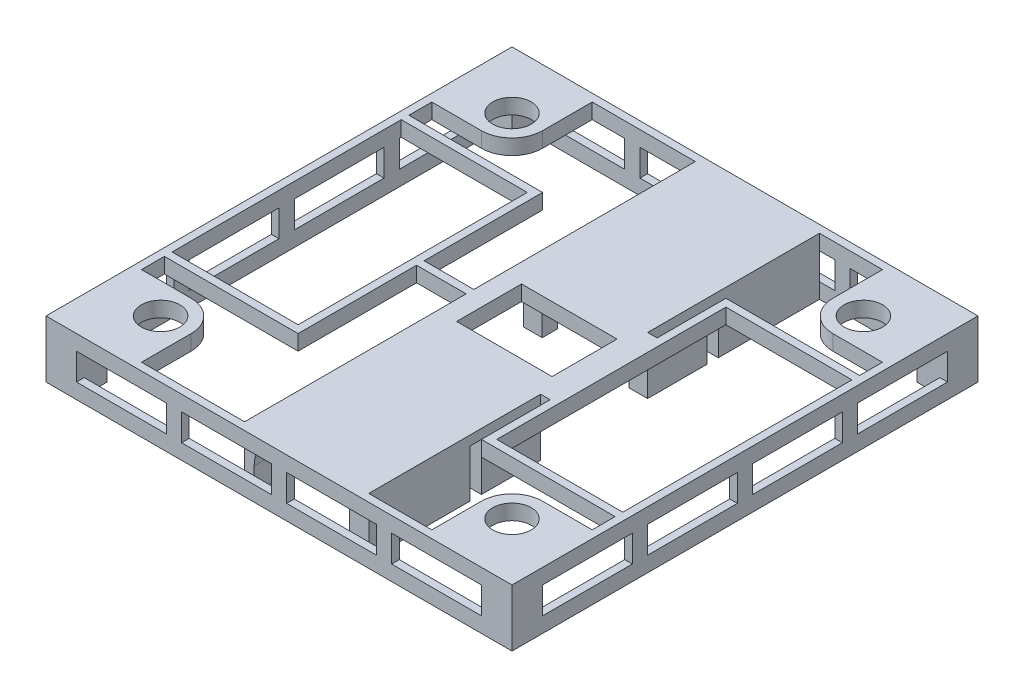
SolidWorks part; units mm, degrees
ref_plane "Front Plane" through (0, 0, 0) normal (0, 0, 1) x (1, 0, 0)
ref_plane "Top Plane" through (0, 0, 0) normal (0, 1, 0) x (1, 0, 0)
ref_plane "Right Plane" through (0, 0, 0) normal (1, 0, 0) x (0, 0, -1)
sketch "Sketch1" plane through (0, 0, 0) normal (0, 1, 0) x (1, 0, 0)
  line L0 (0, 0) -> (122, 0)
  line L1 (0, 0) -> (0, 122)
  line L2 (122, 0) -> (122, 122)
  line L3 (0, 122) -> (122, 122)
  line L4 (2, 2) -> (120, 2)
  line L5 (120, 2) -> (120, 120)
  line L6 (2, 120) -> (120, 120)
  line L7 (2, 2) -> (2, 120)
  dimension "D1" = 2
extrude "Boss-Extrude2" add sketch "Sketch1" along normal blind 15 contours L3 L1 L0 L2 L4 L7 L6 L5 region at (1.7253, 0, -61)
sketch "Sketch4" plane through (0, 0, 0) normal (0, 0, 1) x (1, 0, 0)
  line L0 (0, 15) -> (8, 15)
  line L1 (0, 15) -> (122, 15) construction
  line L2 (8, 15) -> (8, 0)
  line L3 (0, 0) -> (122, 0) construction
  line L4 (8, 15) -> (8, 11)
  line L5 (8, 11) -> (114, 11)
  line L6 (114, 11) -> (114, 4)
  line L7 (114, 4) -> (8, 4)
extrude "Cut-Extrude1" cut sketch "Sketch4" against normal through all both and the other way through all contours L7 L6 L5 L2 region at (61, 7.5, 0)
sketch "Sketch5" plane through (0, 0, 0) normal (-1, 0, 0) x (0, 0, 1)
  line L0 (-122, 15) -> (-114, 15)
  line L1 (0, 15) -> (-122, 15) construction
  line L2 (-114, 15) -> (-114, 0)
  line L3 (0, 0) -> (-122, 0) construction
  line L4 (-114, 0) -> (-8, 0)
  line L5 (-8, 0) -> (-8, 11)
  line L6 (-8, 11) -> (-114, 11)
  line L7 (-114, 11) -> (-114, 4)
  line L8 (-114, 4) -> (-8, 4)
extrude "Cut-Extrude2" cut sketch "Sketch5" against normal through all both and the other way through all contours L2 L8 L5 L6 region at (0, 7.5, -61)
sketch "Sketch6" plane through (0, 15, 0) normal (0, 1, 0) x (1, 0, 0)
  line L0 (0, 122) -> (8, 122)
  line L1 (0, 122) -> (0, 114)
  line L2 (8, 122) -> (8, 114)
  line L3 (0, 114) -> (8, 114)
  line L4 (0, 122) -> (122, 122) construction
  line L5 (61, 122) -> (61, 110.513)
  line L6 (122, 61) -> (106.27, 61)
  line L7 (122, 0) -> (122, 122) construction
  line L8 (122, 114) -> (114, 114)
  line L9 (114, 122) -> (114, 114)
  line L10 (122, 122) -> (122, 114)
  line L11 (122, 122) -> (114, 122)
  line L12 (122, 0) -> (114, 0)
  line L13 (122, 0) -> (122, 8)
  line L14 (114, 0) -> (114, 8)
  line L15 (122, 8) -> (114, 8)
  line L16 (61, 0) -> (61, 11.487)
  line L17 (0, 8) -> (8, 8)
  line L18 (8, 0) -> (8, 8)
  line L19 (0, 0) -> (0, 8)
  line L20 (0, 0) -> (8, 0)
  line M11 (120, 2) -> (2, 2)
  line M12 (2, 2) -> (2, 120)
  line M13 (2, 120) -> (120, 120)
  line M14 (120, 120) -> (120, 2)
extrude "Boss-Extrude3" add sketch "Sketch6" against normal blind 15 contours L3 L2 M12 M13 | L9 L8 M13 M14 | L15 L14 M14 M11 | L18 L17 M11 M12 region at (5, 15, -117) region at (5, 15, -5) region at (117, 15, -117) region at (117, 15, -5)
sketch "Sketch7" plane through (0, 15, 0) normal (0, 1, 0) x (1, 0, 0)
  line L3 (15, 99) -> (0, 99)
  line L5 (0, 0) -> (0, 122) construction
  line L6 (23, 107) -> (23, 122)
  line L7 (0, 122) -> (122, 122) construction
  line L8 (23, 122) -> (0, 122)
  line L9 (0, 122) -> (0, 99)
  line L10 (61, 122) -> (61, 61)
  line L11 (107, 99) -> (122, 99)
  line L12 (122, 99) -> (122, 122)
  line L13 (122, 122) -> (99, 122)
  line L14 (99, 107) -> (99, 122)
  line L15 (99, 15) -> (99, 0)
  line L16 (99, 0) -> (122, 0)
  line L17 (122, 0) -> (122, 23)
  line L18 (107, 23) -> (122, 23)
  line L19 (15, 23) -> (0, 23)
  line L20 (0, 23) -> (0, 0)
  line L21 (0, 0) -> (23, 0)
  line L22 (23, 15) -> (23, 0)
  circle A0 centre (15, 107) radius 1.5
  circle A1 centre (15, 107) radius 8
  circle A2 centre (107, 107) radius 8
  circle A3 centre (107, 107) radius 1.5
  circle A4 centre (107, 15) radius 8
  circle A5 centre (107, 15) radius 1.5
  circle A6 centre (15, 15) radius 8
  circle A7 centre (15, 15) radius 1.5
  point P43 (61, 61)
  line M6 (114, 2) -> (8, 2)
  line M7 (8, 2) -> (8, 8)
  line M8 (8, 8) -> (2, 8)
  line M9 (2, 8) -> (2, 114)
  line M10 (2, 114) -> (8, 114)
  line M11 (8, 114) -> (8, 120)
  line M12 (8, 120) -> (114, 120)
  line M13 (114, 120) -> (114, 114)
  line M14 (114, 114) -> (120, 114)
  line M15 (120, 114) -> (120, 8)
  line M16 (120, 8) -> (114, 8)
  line M17 (114, 8) -> (114, 2)
  dimension "D1" = 4
extrude "Boss-Extrude4" add sketch "Sketch7" against normal blind 4 contours A1 L6 L3 M12 M11 M10 M9 | A1 A0 | A2 L11 L14 M15 M14 M13 M12 | A2 A3 | A4 A5 | A4 L15 L18 M6 M17 M16 M15 | A6 L19 L22 M9 M8 M7 M6 | A6 A7 region at (8.5, 15, -99.297) region at (9.5031, 15, -112.4969) region at (8.5, 15, -22.703) region at (20.4969, 15, -20.4969) region at (106.5, 15, -119.703) region at (107, 15, -114.7737) region at (99.297, 15, -8.5) region at (101.5031, 15, -20.4969)
sketch "Sketch8" plane through (0, 15, 0) normal (0, 1, 0) x (1, 0, 0)
  circle A0 centre (15, 15) radius 5.05
  circle A1 centre (107, 15) radius 5.05
  circle A2 centre (107, 107) radius 5.05
  circle A3 centre (15, 107) radius 5.05
extrude "Cut-Extrude3" cut sketch "Sketch8" against normal blind 4
sketch "Sketch9" plane through (122, 0, 0) normal (1, 0, 0) x (0, 0, -1)
  line L1 (8, 11) -> (8, 4)
  line L2 (114, 11) -> (114, 4)
  line L3 (8, 4) -> (114, 4)
  line L4 (61, 11) -> (61, 4)
  line L5 (61, 11) -> (63, 11)
  line L6 (63, 11) -> (63, 4)
  line L7 (63, 4) -> (59, 4)
  line L8 (59, 4) -> (59, 11)
  line L9 (8, 11) -> (6, 11)
  line L10 (6, 11) -> (61, 11)
  line L11 (6, 11) -> (61, 11)
  line L12 (35.5, 11) -> (35.5, 4)
  line L13 (31.5, 4) -> (31.5, 11)
  line L14 (33.5, 11) -> (35.5, 11)
  line L15 (35.5, 4) -> (31.5, 4)
  line L16 (33.5, 11) -> (33.5, 4)
  line L17 (88.5, 11) -> (90.5, 11)
  line L18 (90.5, 4) -> (86.5, 4)
  line L19 (88.5, 11) -> (88.5, 4)
  line L20 (90.5, 11) -> (90.5, 4)
  line L21 (86.5, 4) -> (86.5, 11)
  line M6 (8, 11) -> (114, 11)
extrude "Boss-Extrude5" add sketch "Sketch9" against normal blind 122 contours L16 L11 L13 L15 | L16 L3 L12 M6 | L6 L4 L3 M6 | L8 L3 L4 M6 | L20 L19 L3 M6 | L21 L18 L19 M6 region at (122, 7.5, -32.5) region at (122, 7.5, -34.5) region at (122, 7.5, -60) region at (122, 7.5, -62) region at (122, 7.5, -87.5) region at (122, 7.5, -89.5)
sketch "Sketch10" plane through (0, 0, 0) normal (0, -1, 0) x (1, 0, 0)
  line L0 (2, -31.5) -> (120, -31.5)
  line L1 (2, -31.5) -> (2, -92.7196)
  line L2 (120, -31.5) -> (120, -92.7196)
  line L3 (2, -92.7196) -> (120, -92.7196)
extrude "Cut-Extrude4" cut sketch "Sketch10" against normal through all both and the other way through all
sketch "Sketch11" plane through (0, 0, -122) normal (0, 0, -1) x (-1, 0, 0)
  line L0 (-61, 11) -> (-116, 11)
  line L1 (-8, 11) -> (-114, 11) construction
  line L2 (-88.5, 11) -> (-88.5, 4)
  line L3 (-114, 4) -> (-8, 4) construction
  line L4 (-88.5, 4) -> (-86.5, 4)
  line L5 (-86.5, 4) -> (-86.5, 11)
  line L6 (-86.5, 11) -> (-90.5, 11)
  line L7 (-90.5, 11) -> (-90.5, 4)
  line L8 (-90.5, 4) -> (-88.5, 4)
  line L9 (-59, 11) -> (-63, 11)
  line L10 (-61, 4) -> (-59, 4)
  line L11 (-59, 4) -> (-59, 11)
  line L12 (-63, 11) -> (-63, 4)
  line L13 (-61, 11) -> (-61, 4)
  line L14 (-63, 4) -> (-61, 4)
  line L15 (-31.5, 11) -> (-35.5, 11)
  line L16 (-33.5, 4) -> (-31.5, 4)
  line L17 (-31.5, 4) -> (-31.5, 11)
  line L18 (-35.5, 11) -> (-35.5, 4)
  line L19 (-33.5, 11) -> (-33.5, 4)
  line L20 (-35.5, 4) -> (-33.5, 4)
  line M6 (-8, 4) -> (-114, 4)
  line M8 (-114, 11) -> (-8, 11)
extrude "Boss-Extrude6" add sketch "Sketch11" against normal blind 122 contours L0 L7 L2 M6 | L5 L0 L2 M6 | L13 L11 M8 M6 | L13 L0 L12 M6 | L15 L19 L17 M6 | L19 L18 M8 M6 region at (62, 7.5, -122) region at (60, 7.5, -122) region at (87.5, 7.5, -122) region at (34.5, 7.5, -122) region at (89.5, 7.5, -122) region at (32.5, 7.5, -122)
sketch "Sketch12" plane through (0, 15, 0) normal (0, 1, 0) x (1, 0, 0)
  line L0 (99, 2) -> (23, 2)
  line L1 (99, 2) -> (99, 120)
  line L2 (23, 2) -> (23, 120)
  line L3 (99, 120) -> (23, 120)
extrude "Cut-Extrude5" cut sketch "Sketch12" against normal blind 122
sketch "Sketch13" plane through (0, 15, 0) normal (0, 1, 0) x (1, 0, 0)
  line L0 (61, 0) -> (61, 122)
  line L1 (0, 0) -> (122, 0) construction
  line L2 (0, 122) -> (122, 122) construction
  line L3 (15, 15) -> (107, 15)
  line L4 (61, 15) -> (61, 20)
  line L10 (61, 20) -> (56, 20)
  line L11 (56, 20) -> (56, 10)
  line L12 (56, 10) -> (66, 10)
  line L13 (66, 10) -> (66, 20)
  line L14 (66, 20) -> (61, 20)
  line L15 (61, 20) -> (61, 24.5)
  line L16 (61, 24.5) -> (55, 24.5)
  line L17 (61, 24.5) -> (69.5, 24.5)
  line L18 (69.5, 24.5) -> (69.5, 20)
  line L19 (69.5, 20) -> (66, 20)
  line L20 (56, 20) -> (55, 20)
  line L21 (55, 20) -> (55, 24.5)
  line L22 (55, 24.5) -> (55, 28.5)
  line L23 (55, 28.5) -> (50, 28.5)
  line L24 (50, 28.5) -> (50, 31)
  line L25 (50, 31) -> (55, 31)
  line L26 (55, 31) -> (55, 47)
  line L27 (55, 47) -> (77.5, 47)
  line L28 (77.5, 47) -> (77.5, 31)
  line L29 (77.5, 31) -> (82.5, 31)
  line L30 (82.5, 31) -> (82.5, 28.5)
  line L31 (82.5, 28.5) -> (77.5, 28.5)
  line L32 (77.5, 28.5) -> (77.5, 24.5)
  line L33 (77.5, 24.5) -> (69.5, 24.5)
  line L34 (61, 61) -> (120, 61)
  line L35 (120, 23) -> (120, 99) construction
  line L36 (61, 61) -> (2, 61)
  line L37 (2, 23) -> (2, 99) construction
  line L38 (62, 0) -> (62, 122)
  line L39 (61, 60) -> (2, 60)
  line L40 (61, 60) -> (120, 60)
  line L41 (60, 0) -> (60, 122)
  line L42 (61, 62) -> (2, 62)
  line L43 (61, 62) -> (120, 62)
  line L44 (77.5, 61) -> (77.5, 47)
  line L45 (82.5, 31) -> (82.5, 61)
  line L46 (82.5, 61) -> (82.5, 2)
  line L47 (23, 2) -> (99, 2) construction
  line L48 (82.5, 2) -> (77.5, 2)
  line L49 (77.5, 2) -> (77.5, 24.5)
  line L50 (55, 31) -> (55, 61)
  line L51 (55, 20) -> (55, 2)
  line L52 (55, 2) -> (50, 2)
  line L53 (50, 2) -> (50, 60)
  line M17 (99, 2) -> (23, 2)
  line M21 (2, 23) -> (2, 99)
  line M25 (23, 120) -> (99, 120)
  line M29 (120, 99) -> (120, 23)
  dimension "D1" = 1
  dimension "D2" = 1
extrude "Boss-Extrude7" add sketch "Sketch13" against normal blind 4 contours L41 L42 L36 M21 | L39 L50 L36 M21 | L50 L39 L41 L36 | L53 L25 L26 L50 L39 | L0 L42 L41 L36 | L41 L39 L0 L36 | L43 L0 L34 L38 | L0 L40 L38 L34 | L42 L0 L41 M25 | L0 L43 L38 M25 | L43 L38 L34 M29 | L44 L34 L38 L40 | L40 L0 L27 L38 | L41 L27 L0 L39 | L40 L45 L34 L44 | L45 L40 L34 M29 | L29 L45 L40 L44 L28 | L41 L16 L0 L27 | L17 L38 L27 L0 | L41 L10 L0 L16 | L14 L38 L17 L0 | L53 L3 L51 L21 L22 L23 | L41 L3 L0 L10 | L3 L38 L14 L0 | L41 L12 L0 L3 | L12 L38 L3 L0 | L38 L12 L0 M17 | L41 L0 L12 M17 | L49 L3 L46 L31 L32 | L49 L46 L3 M17 | L53 L51 L3 M17 region at (60.5, 15, -17.5) region at (61.5, 15, -12.5) region at (60.5, 15, -12.5) region at (61.5, 15, -17.5) region at (60.5, 15, -22.25) region at (61.5, 15, -22.25) region at (61.5, 15, -6) region at (60.5, 15, -6) region at (60.5, 15, -35.75) region at (61.5, 15, -35.75) region at (60.5, 15, -53.5) region at (61.5, 15, -53.5) region at (52.5, 15, -8.5) region at (52.5, 15, -21.75) region at (80, 15, -21.75) region at (80, 15, -8.5) region at (60.5, 15, -60.5) region at (61.5, 15, -60.5) region at (60.5, 15, -61.5) region at (61.5, 15, -61.5) region at (57.5, 15, -60.5) region at (69.75, 15, -60.5) region at (52.5, 15, -45.5) region at (80, 15, -45.5) region at (60.5, 15, -91) region at (61.5, 15, -91) region at (91, 15, -61.5) region at (31, 15, -61.5) region at (28.5, 15, -60.5) region at (80, 15, -60.5) region at (101.25, 15, -60.5)
sketch "Sketch14" plane through (0, 15, 0) normal (0, 1, 0) x (1, 0, 0)
  line L0 (77.5, 47) -> (55, 47)
  line L1 (55, 47) -> (55, 49)
  line L2 (55, 49) -> (77.5, 49)
  line L3 (77.5, 49) -> (82.5, 49)
  line L4 (82.5, 49) -> (82.5, 2)
  line L5 (82.5, 2) -> (77.5, 2)
  line L6 (77.5, 2) -> (77.5, 47)
  line L7 (55, 49) -> (50, 49)
  line L8 (50, 49) -> (50, 2)
  line L9 (50, 2) -> (55, 2)
  line L10 (55, 2) -> (55, 47)
  line L11 (69.5, 20) -> (69.5, 24.5)
  line L12 (69.5, 24.5) -> (77.5, 24.5)
  line L13 (69.5, 20) -> (77.5, 20)
extrude "Boss-Extrude8" add sketch "Sketch14" against normal blind 15 contours L9 L10 L1 L7 L8 | L6 L5 L4 L3 L2 L1 L0 | L11 L13 L6 L12 region at (77.7902, 15, -29.1161) region at (52.5, 15, -25.5) region at (73.5, 15, -22.25)
sketch "Sketch16" plane through (0, 0, -24.5) normal (0, 0, -1) x (-1, 0, 0)
  line L0 (-69.5, 0) -> (-55, 0)
  line L1 (-55, 0) -> (-55, 12.5)
  line L2 (-55, 12.5) -> (-69.5, 12.5)
  line L3 (-69.5, 0) -> (-69.5, 15) construction
  line L4 (-69.5, 12.5) -> (-69.5, 0)
  line L5 (-55, 12.5) -> (-61, 12.5)
  line L6 (-61, 12.5) -> (-61, 6.25)
  line L7 (-61, 6.25) -> (-66.5, 6.25)
  line L8 (-66.5, 9.25) -> (-66.5, 3.25)
  line L9 (-66.5, 9.25) -> (-61, 9.25)
  line L10 (-66.5, 3.25) -> (-61, 3.25)
  line L11 (-61, 9.25) -> (-61, 3.25)
  circle A0 centre (-66.5, 6.25) radius 3
  circle A1 centre (-61, 6.25) radius 6
  line M16 (-69.5, 0) -> (-69.5, 15)
extrude "Boss-Extrude11" add sketch "Sketch16" against normal blind 4.5 contours A1 L6 L2 L4 A0 L9 | A1 L1 L2 L6 | A1 L10 A0 L0 L1 M16 region at (69.3421, 3.125, -24.5) region at (66.9472, 10.8714, -24.5) region at (56.6101, 11.148, -24.5)
sketch "Sketch17" plane through (0, 12.5, 0) normal (0, 1, 0) x (1, 0, 0)
  line L0 (55, 20) -> (55, 24.5)
  line L1 (55, 20) -> (69.5, 20)
  line L2 (55, 24.5) -> (69.5, 24.5)
  line L3 (69.5, 20) -> (69.5, 24.5)
  line L4 (55, 24.5) -> (60, 24.5) construction
  line L5 (55, 20) -> (55, 24.5) construction
extrude "Boss-Extrude12" add sketch "Sketch17" along normal blind 2.5
sketch "Sketch18" plane through (0, 11, 0) normal (0, -1, 0) x (1, 0, 0)
  line L0 (62, -2) -> (62, -47)
  line L1 (62, -2) -> (60, -2)
  line L2 (62, -47) -> (60, -47)
  line L3 (60, -2) -> (60, -47)
  line L4 (62, -2) -> (62, -47) construction
extrude "Cut-Extrude6" cut sketch "Sketch18" against normal blind 2
sketch "Sketch19" plane through (55, 0, 0) normal (1, 0, 0) x (0, 0, -1)
  line L0 (47, 0) -> (47, 12.5)
  line L1 (47, 12.5) -> (2, 12.5)
  line L2 (2, 11) -> (2, 15) construction
  line L3 (2, 12.5) -> (2, 15)
  line L4 (2, 15) -> (47, 15)
  line L5 (47, 15) -> (47, 12.5)
  line M1 (47, 15) -> (24.5, 15)
  line M2 (24.5, 15) -> (24.5, 6.25)
  line M5 (47, 0) -> (47, 15)
extrude "Boss-Extrude13" add sketch "Sketch19" along normal blind 25 contours L4 L3 L1 M2 | L1 M5 M1 M2 region at (55, 13.75, -35.75) region at (55, 13.75, -13.25)
sketch "Sketch21" plane through (0, 0, 0) normal (0, -1, 0) x (1, 0, 0)
  line L0 (77.5, -24.5) -> (77.5, -28.5)
  line L1 (77.5, -24.5) -> (77.5, -47) construction
  line L2 (77.5, -28.5) -> (82.5, -28.5)
  line L3 (82.5, -49) -> (82.5, -2) construction
  line L4 (82.5, -28.5) -> (82.5, -31)
  line L5 (82.5, -31) -> (50, -31)
  line L6 (50, -49) -> (50, -2) construction
  line L7 (50, -31) -> (50, -28.5)
  line L8 (50, -28.5) -> (77.5, -28.5)
  line M1 (55, -47) -> (55, -24.5)
  line M3 (77.5, -24.5) -> (77.5, -47)
  line M11 (50, -2) -> (50, -49)
  line M13 (82.5, -49) -> (82.5, -2)
extrude "Cut-Extrude7" cut sketch "Sketch21" against normal blind 12.5 contours L5 L2 M13 M3 | L8 L5 M11 M1 region at (80, 0, -29.75) region at (52.5, 0, -29.75)
sketch "Sketch26" plane through (0, 12.5, 0) normal (0, -1, 0) x (1, 0, 0)
  line L0 (55, -20) -> (47.6546, -20)
  line L1 (55, -20) -> (55, -2)
  line L2 (47.6546, -20) -> (47.6546, -2)
  line L3 (55, -2) -> (47.6546, -2)
extrude "Cut-Extrude8" cut sketch "Sketch26" along normal blind 25
sketch "Sketch27" plane through (0, 0, -20) normal (0, 0, 1) x (1, 0, 0)
  line L0 (50, 0) -> (50, 12.5)
  line L1 (50, 0) -> (55.7303, 0)
  line L2 (50, 12.5) -> (55.7303, 12.5)
  line L3 (55.7303, 0) -> (55.7303, 12.5)
  circle A0 centre (61, 6.25) radius 8.5
  line M10 (50, 12.5) -> (50, 0)
  line M11 (50, 0) -> (77.5, 0)
extrude "Boss-Extrude14" add sketch "Sketch27" along normal blind 18 contours A0 L2 M10 M11 region at (51.7659, 6.25, -20)
sketch "Sketch29" plane through (0, 0, -20) normal (0, 0, 1) x (1, 0, 0)
  circle A0 centre (61, 6.25) radius 8.5
extrude "Cut-Extrude9" cut sketch "Sketch29" along normal blind 18
sketch "Sketch30" plane through (0, 0, 0) normal (0, -1, 0) x (1, 0, 0)
  line L0 (55, -24.5) -> (77.5, -24.5)
  line L1 (55, -24.5) -> (55, -20)
  line L2 (77.5, -24.5) -> (77.5, -20)
  line L3 (55, -20) -> (77.5, -20)
extrude "Cut-Extrude10" cut sketch "Sketch30" against normal blind 6.35
sketch "Sketch31" plane through (0, 0, -20) normal (0, 0, -1) x (-1, 0, 0)
  line L0 (-55, 0) -> (-55.2391, 0)
  line L1 (-55, 0) -> (-55, 0.3342)
  line L2 (-55.2391, 0) -> (-55.2391, 0.3342)
  line L3 (-55, 0.3342) -> (-55.2391, 0.3342)
extrude "Cut-Extrude11" cut sketch "Sketch31" against normal up to surface (18 mm away) up to face at (65.1774, 7.3143, -2)
sketch "Sketch32" plane through (0, 0, -2) normal (0, 0, 1) x (1, 0, 0)
  line L0 (52.5, 6.25) -> (61, 6.25)
  line L1 (52.5, 6.25) -> (52.5, -7.1759)
  line L2 (61, 6.25) -> (61, -7.1759)
  line L3 (52.5, -7.1759) -> (61, -7.1759)
  arc A0 (53.9511, 11) -> (52.8032, 4) centre (61, 6.25) ccw construction
extrude "Cut-Extrude12" cut sketch "Sketch32" against normal up to surface (18 mm away) up to face at (63.6001, 9.7082, -20)
sketch "Sketch34" plane through (0, 0, 0) normal (0, -1, 0) x (1, 0, 0)
  line L0 (55, -47) -> (55, -43)
  line L1 (55, -31) -> (55, -47) construction
  line L2 (55, -43) -> (50, -43)
  line L3 (50, -49) -> (50, -31) construction
  line L4 (50, -43) -> (50, -41)
  line L5 (50, -41) -> (55, -41)
  line L6 (55, -41) -> (55, -43)
  line M4 (55, -47) -> (55, -31)
  line M6 (50, -31) -> (50, -49)
extrude "Cut-Extrude13" cut sketch "Sketch34" against normal up to surface (12.5 mm away) contours L5 L2 M6 M4 region at (52.5, 0, -42) up to face at (64.9375, 12.5, -29.375)
sketch "Sketch36" plane through (0, 15, 0) normal (0, 1, 0) x (1, 0, 0)
  line L0 (2, 60) -> (2, 62)
  line L1 (2, 62) -> (2, 61)
  line L2 (2, 61) -> (2, 31)
  line L3 (2, 31) -> (35, 31)
  line L4 (35, 31) -> (35, 91)
  line L5 (35, 91) -> (2, 91)
  line L6 (2, 62) -> (2, 99) construction
  line L7 (2, 91) -> (2, 62)
  line M15 (2, 60) -> (50, 60)
  line M29 (60, 62) -> (2, 62)
extrude "Cut-Extrude14" cut sketch "Sketch36" against normal blind 6.35 contours L4 L0 M15 M29 region at (18.5, 15, -61)
sketch "Sketch37" plane through (0, 15, 0) normal (0, 1, 0) x (1, 0, 0)
  line L0 (35, 62) -> (35, 91)
  line L1 (35, 91) -> (2, 91)
  line L2 (2, 23) -> (2, 99) construction
  line L3 (2, 91) -> (2, 93)
  line L4 (2, 93) -> (37, 93)
  line L5 (37, 93) -> (37, 29)
  line L6 (37, 29) -> (2, 29)
  line L7 (2, 29) -> (2, 31)
  line L8 (2, 31) -> (35, 31)
  line L9 (35, 31) -> (35, 62)
  line L10 (2, 93) -> (2, 29)
  line M31 (2, 23) -> (2, 99)
  line M37 (60, 62) -> (35, 62)
  line M38 (35, 62) -> (35, 60)
  line M39 (35, 60) -> (50, 60)
extrude "Boss-Extrude15" add sketch "Sketch37" against normal blind 4 contours L5 L4 L1 L0 M31 M37 | L5 M37 M38 M39 | L9 L8 L6 L5 M31 M39 region at (36, 15, -61) region at (35.4675, 15, -76.5) region at (36, 15, -59.5325)
sketch "Sketch38" plane through (0, 15, 0) normal (0, 1, 0) x (1, 0, 0)
  line L0 (120, 60) -> (87, 60)
  line L1 (82.5, 60) -> (120, 60) construction
  line L2 (87, 60) -> (87, 31)
  line L3 (87, 31) -> (120, 31)
  line L4 (120, 23) -> (120, 60) construction
  line L5 (120, 31) -> (120, 29)
  line L6 (120, 29) -> (85, 29)
  line L7 (85, 29) -> (85, 93)
  line L8 (85, 93) -> (120, 93)
  line L9 (120, 62) -> (120, 99) construction
  line L10 (120, 93) -> (120, 91)
  line L11 (120, 91) -> (87, 91)
  line L12 (87, 91) -> (87, 60)
  line L13 (120, 93) -> (120, 91)
  line L14 (120, 31) -> (120, 29)
extrude "Boss-Extrude16" add sketch "Sketch38" against normal blind 4 contours L12 L11 L10 L8 L7 L6 L5 L3 L2 region at (86.2705, 15, -45.5)
sketch "Sketch39" plane through (0, 15, 0) normal (0, 1, 0) x (1, 0, 0)
  line L0 (87, 62) -> (87, 60)
  line L1 (87, 62) -> (120, 62)
  line L2 (87, 60) -> (120, 60)
  line L3 (120, 62) -> (120, 60)
extrude "Cut-Extrude15" cut sketch "Sketch39" against normal blind 4
sketch "Sketch41" plane through (0, 11, 0) normal (0, -1, 0) x (-1, 0, 0)
  line L0 (-82.5, 60) -> (-82.5, 49)
  line L1 (-82.5, 49) -> (-82.5, 62)
  line L2 (-62, 62) -> (-85, 62) construction
  line L3 (-82.5, 62) -> (-82.5, 73)
  line L4 (-82.5, 73) -> (-50, 73)
  line L5 (-50, 73) -> (-50, 79)
  line L6 (-50, 79) -> (-55, 79)
  line L7 (-55, 79) -> (-55, 75)
  line L8 (-55, 75) -> (-77.5, 75)
  line L9 (-77.5, 75) -> (-77.5, 91)
  line L10 (-77.5, 91) -> (-82.5, 91)
  line L11 (-82.5, 91) -> (-82.5, 73)
  line L12 (-82.5, 91) -> (-82.5, 93.5)
  line L13 (-82.5, 93.5) -> (-77.5, 93.5)
  line L14 (-77.5, 93.5) -> (-77.5, 120)
  line L15 (-8, 120) -> (-114, 120) construction
  line L16 (-77.5, 120) -> (-82.5, 120)
  line L17 (-82.5, 120) -> (-82.5, 93.5)
  line L18 (-55, 79) -> (-55, 81)
  line L19 (-55, 81) -> (-50, 81)
  line L20 (-50, 81) -> (-50, 91)
  line L21 (-50, 91) -> (-55, 91)
  line L22 (-55, 91) -> (-55, 81)
  line L23 (-55, 91) -> (-55, 93.5)
  line L24 (-55, 93.5) -> (-50, 93.5)
  line L25 (-50, 93.5) -> (-50, 120)
  line L26 (-50, 120) -> (-55, 120)
  line L27 (-55, 120) -> (-55, 93.5)
  line L28 (-55, 93.5) -> (-55, 102)
extrude "Boss-Extrude17" add sketch "Sketch41" along normal blind 11 and the other way blind 4 contours L10 L11 L4 L5 L6 L7 L8 L9 | L16 L17 L13 L14 | L21 L22 L19 L20 | L26 L27 L24 L25 region at (82.1285, 11, -82) region at (80, 11, -106.75) region at (52.5, 11, -106.75) region at (52.5, 11, -86)
sketch "Sketch42" plane through (0, 15, 0) normal (0, 1, 0) x (1, 0, 0)
  line L0 (50, 73) -> (50, 120)
  line L1 (50, 73) -> (82.5, 73)
  line L2 (50, 120) -> (82.5, 120)
  line L3 (82.5, 73) -> (82.5, 120)
  line L4 (82.5, 73) -> (82.5, 62)
  line L5 (62, 62) -> (85, 62) construction
  line L6 (82.5, 62) -> (77.5, 62)
  line L7 (77.5, 62) -> (77.5, 73)
  line L8 (77.5, 73) -> (82.5, 73)
  line L9 (50, 73) -> (50, 62)
  line L10 (60, 62) -> (37, 62) construction
  line L11 (50, 62) -> (55, 62)
  line L12 (55, 62) -> (55, 73)
extrude "Boss-Extrude18" add sketch "Sketch42" against normal blind 2.5 contours L1 L3 L2 L0 | L7 L6 L4 L1 | L11 L12 L1 L9 region at (66.25, 15, -96.5) region at (52.5, 15, -67.5) region at (80, 15, -67.5)
sketch "Sketch46" plane through (0, 12.5, 0) normal (0, -1, 0) x (1, 0, 0)
  line L0 (82.5, -62) -> (77.5, -62)
  line L1 (82.5, -62) -> (82.5, -73)
  line L2 (77.5, -62) -> (77.5, -73)
  line L3 (82.5, -73) -> (77.5, -73)
  line L4 (82.5, -62) -> (77.5, -62) construction
  line L5 (55, -73) -> (50, -73)
  line L6 (55, -73) -> (55, -62)
  line L7 (50, -73) -> (50, -62)
  line L8 (55, -62) -> (50, -62)
extrude "Boss-Extrude19" add sketch "Sketch46" along normal blind 1.5
sketch "Sketch47" plane through (0, 11, 0) normal (0, -1, 0) x (1, 0, 0)
  line L0 (62, -75) -> (60, -75)
  line L1 (62, -75) -> (62, -120)
  line L2 (60, -75) -> (60, -120)
  line L3 (62, -120) -> (60, -120)
extrude "Cut-Extrude16" cut sketch "Sketch47" against normal blind 1.5
sketch "Sketch50" plane through (0, 12.5, 0) normal (0, -1, 0) x (1, 0, 0)
  line L0 (77.5, -75) -> (77.5, -97.6)
  line L1 (77.5, -93.5) -> (77.5, -120) construction
  line L2 (77.5, -97.6) -> (55, -97.6)
  line L3 (55, -120) -> (55, -93.5) construction
  line L4 (55, -97.6) -> (55, -102.6)
  line L5 (55, -102.6) -> (77.5, -102.6)
  line L6 (77.5, -102.6) -> (77.5, -97.6)
  line M5 (55, -93.5) -> (55, -120)
  line M7 (77.5, -120) -> (77.5, -93.5)
extrude "Boss-Extrude21" add sketch "Sketch50" along normal blind 6.15 contours L5 L2 M5 M7 region at (66.25, 12.5, -100.1)
sketch "Sketch53" plane through (0, 0, -97.6) normal (0, 0, 1) x (1, 0, 0)
  line L0 (55, 12.5) -> (55, 0)
  line L1 (55, 0) -> (67, 0)
  line L2 (67, 0) -> (67, 12.5)
  line L3 (77.5, 12.5) -> (55, 12.5) construction
  line L4 (67, 12.5) -> (55, 12.5)
  line L5 (61, 0) -> (61, 6.25)
  line L6 (61, 6.25) -> (66.5, 6.25)
  line L7 (66.5, 3.25) -> (61, 3.25)
  line L8 (66.5, 9.25) -> (63.3151, 9.25)
  circle A0 centre (61, 6.25) radius 6.0008
  circle A1 centre (66.5, 6.25) radius 3
  line M9 (55, 6.35) -> (77.5, 6.35)
extrude "Cut-Extrude17" cut sketch "Sketch53" against normal blind 6.15 contours A1 A0 L2 M9 | A1 L6 L5 L7 A0 | A1 L0 A0 L5 L6 M9 | A1 A0 M9 | A1 L2 M9 | L2 A1 A0 M9 | L2 A1 A0 | A0 A1 L2 | A1 A0 L7 | A1 L8 A0 | L5 A0 L7 | A1 region at (58.4764, 3.7789, -97.6) region at (60.321, 9.0571, -97.6) region at (66.2759, 9.2456, -97.6) region at (65.3618, 5.0861, -97.6) region at (68.0379, 7.519, -97.6) region at (66.7619, 8.5047, -97.6) region at (63.0356, 2.0195, -97.6) region at (62.6426, 4.5803, -97.6) region at (68.0561, 5.0898, -97.6) region at (66.2759, 3.2544, -97.6) region at (66.7619, 3.9953, -97.6)
sketch "Sketch54" plane through (0, 0, -102.6) normal (0, 0, -1) x (-1, 0, 0)
  circle A0 centre (-61, 6.25) radius 8.5
extrude "Cut-Extrude18" cut sketch "Sketch54" along normal up to surface (17.4 mm away) up to face at (33, 7.5, -120)
sketch "Sketch57" plane through (0, 0, 0) normal (0, -1, 0) x (1, 0, 0)
  line L0 (82.5, -2) -> (82.5, -49)
  line L1 (82.5, -49) -> (82.5, -73)
  line L2 (82.5, -73) -> (82.5, -120)
  line L3 (82.5, -73) -> (82.5, -75)
  line L4 (82.5, -75) -> (50, -75)
  line L5 (50, -73) -> (50, -79) construction
  line L6 (50, -75) -> (50, -47)
  line L7 (50, -49) -> (50, -43) construction
  line L8 (50, -47) -> (82.5, -47)
  line M2 (50, -43) -> (50, -49)
  line M3 (50, -49) -> (82.5, -49)
  line M4 (82.5, -49) -> (82.5, -31)
  line M7 (77.5, -47) -> (55, -47)
extrude "Cut-Extrude20" cut sketch "Sketch57" against normal up to surface (12.5 mm away) contours L8 M2 M3 M4 M7 | L6 L4 L2 L1 M3 region at (66.25, 0, -48) region at (66.25, 0, -62) up to face at (62.8125, 12.5, -87.7)
sketch "Sketch58" plane through (0, 12.5, 0) normal (0, -1, 0) x (1, 0, 0)
  line L0 (77.5, -49) -> (77.5, -73)
  line L1 (77.5, -49) -> (55, -49)
  line L2 (77.5, -73) -> (55, -73)
  line L3 (55, -49) -> (55, -73)
extrude "Cut-Extrude21" cut sketch "Sketch58" against normal through all both and the other way through all
sketch "Sketch62" plane through (0, 12.5, 0) normal (0, -1, 0) x (1, 0, 0)
  line L0 (82.5, -47) -> (82.5, -75)
  line L1 (82.5, -47) -> (50, -47)
  line L2 (82.5, -75) -> (50, -75)
  line L3 (50, -47) -> (50, -75)
  line L4 (77.5, -49) -> (77.5, -73)
  line L5 (77.5, -49) -> (55, -49)
  line L6 (77.5, -73) -> (55, -73)
  line L7 (55, -49) -> (55, -73)
extrude "Boss-Extrude22" add sketch "Sketch62" along normal blind 1.5
sketch "Sketch63" plane through (0, 11, 0) normal (0, -1, 0) x (-1, 0, 0)
  line L0 (-82.5, 47) -> (-85, 47)
  line L1 (-85, 29) -> (-85, 60) construction
  line L2 (-85, 47) -> (-82.5, 75)
  line L3 (-82.5, 75) -> (-85, 75)
  line L4 (-85, 62) -> (-85, 93) construction
  line L5 (-85, 75) -> (-85, 47)
  line L6 (-55, 49) -> (-80, 49)
  line L7 (-80, 49) -> (-80, 73)
  line L8 (-80, 73) -> (-77.5, 73)
  line L9 (-77.5, 73) -> (-77.5, 49)
  line L10 (-82.5, 47) -> (-82.5, 75)
extrude "Boss-Extrude23" add sketch "Sketch63" against normal blind 4 contours L0 L10 L2 | L3 L5 L2 region at (83.3333, 11, -56.3333) region at (84.1667, 11, -65.6667)
sketch "Sketch64" plane through (0, 11, 0) normal (0, -1, 0) x (1, 0, 0)
  line L0 (55, -61) -> (80, -61)
  line L1 (55, -49) -> (55, -73) construction
  line L2 (80, -61) -> (80, -52.5)
  line L3 (80, -52.5) -> (55, -52.5)
  line L4 (55, -52.5) -> (55, -61)
  line L5 (55, -61) -> (55, -69.5)
  line L6 (55, -69.5) -> (80, -69.5)
  line L7 (80, -69.5) -> (80, -61)
extrude "Cut-Extrude22" cut sketch "Sketch64" against normal blind 4 contours L3 L4 L0 L2 | L6 L7 L0 L5 region at (67.5, 11, -56.75) region at (67.5, 11, -65.25)
sketch "Sketch65" plane through (0, 11, 0) normal (0, -1, 0) x (-1, 0, 0)
  line L0 (-77.5, 52.5) -> (-55, 52.5)
  line L1 (-55, 49) -> (-55, 73) construction
  line L2 (-55, 52.5) -> (-55, 49)
  line L3 (-55, 49) -> (-77.5, 49)
  line L4 (-77.5, 49) -> (-77.5, 52.5)
  line L5 (-80, 61) -> (-73.3948, 61)
  line L6 (-80, 69.5) -> (-80, 52.5) construction
  line L7 (-77.5, 73) -> (-77.5, 69.5)
  line L8 (-55, 73) -> (-77.5, 73)
  line L9 (-55, 69.5) -> (-55, 73)
  line L10 (-77.5, 69.5) -> (-55, 69.5)
extrude "Boss-Extrude24" add sketch "Sketch65" against normal blind 4 contours L4 L3 L2 L0 | L7 L10 L9 L8 region at (66.25, 11, -50.75) region at (66.25, 11, -71.25)
sketch "Sketch67" plane through (0, 0, -102.6) normal (0, 0, -1) x (-1, 0, 0)
  line L4 (-52.5, 6.25) -> (-52.5, -3.5632)
  line L5 (-52.5, -3.5632) -> (-56.7117, -1.0889)
  circle A1 centre (-61, 6.25) radius 8.5
  arc M13 (-55, 0.2292) -> (-55, 12.2708) centre (-61, 6.25) ccw
extrude "Cut-Extrude23" cut sketch "Sketch67" along normal up to surface (17.4 mm away) contours A1 L5 L4 M13 region at (53.7639, -0.2943, -102.6) up to face at (33, 7.5, -120)
sketch "Sketch68" plane through (0, 0, 0) normal (0, -1, 0) x (1, 0, 0)
  line L0 (82.5, -31) -> (77.5, -31)
  line L1 (82.5, -31) -> (82.5, -31.5)
  line L2 (77.5, -31) -> (77.5, -31.5)
  line L3 (82.5, -31.5) -> (77.5, -31.5)
  line L4 (55, -31) -> (50, -31)
  line L5 (50, -31) -> (50, -31.5)
  line L6 (50, -41) -> (50, -31) construction
  line L7 (50, -31.5) -> (55, -31.5)
  line L8 (55, -31) -> (55, -41) construction
  line L9 (55, -31.5) -> (55, -31)
  line L10 (77.5, -31) -> (77.5, -91)
  line L11 (77.5, -75) -> (77.5, -91) construction
  line L12 (77.5, -91) -> (77.5, -61)
  line L13 (77.5, -61) -> (71.7624, -61)
  line L14 (55, -90.5) -> (55, -91)
  line L15 (50, -90.5) -> (55, -90.5)
  line L16 (50, -91) -> (50, -90.5)
  line L17 (55, -91) -> (50, -91)
  line L18 (82.5, -90.5) -> (77.5, -90.5)
  line L19 (77.5, -91) -> (77.5, -90.5)
  line L20 (82.5, -91) -> (82.5, -90.5)
  line L21 (82.5, -91) -> (77.5, -91)
  line M4 (82.5, -47) -> (82.5, -31)
  line M5 (82.5, -31) -> (77.5, -31)
  line M6 (77.5, -31) -> (77.5, -47)
extrude "Cut-Extrude24" cut sketch "Sketch68" against normal up to surface (12.5 mm away) contours L3 M4 M5 M6 | L7 L9 L4 L5 | L17 L14 L15 L16 | L21 L20 L18 L12 region at (80, 0, -31.25) region at (80, 0, -90.75) region at (52.5, 0, -31.25) region at (52.5, 0, -90.75) up to face at (62.8125, 12.5, -87.7)
sketch "Sketch69" plane through (0, 0, 0) normal (0, -1, 0) x (-1, 0, 0)
  line L0 (-77.5, 31.5) -> (-77.6, 31.5)
  line L1 (-77.5, 31.5) -> (-82.5, 31.5) construction
  line L2 (-77.6, 31.5) -> (-77.6, 47)
  line L3 (-77.5, 47) -> (-82.5, 47) construction
  line L4 (-77.6, 47) -> (-77.5, 47)
  line L5 (-77.5, 47) -> (-77.5, 31.5)
  line L6 (-55, 31.5) -> (-54.9, 31.5)
  line L7 (-50, 31.5) -> (-55, 31.5) construction
  line L8 (-54.9, 31.5) -> (-54.9, 47)
  line L9 (-50, 47) -> (-55, 47) construction
  line L10 (-54.9, 47) -> (-55, 47)
  line L11 (-55, 47) -> (-55, 31.5)
  line L12 (-80, 61) -> (-77.55, 61)
  line L13 (-80, 69.5) -> (-80, 52.5) construction
  line L14 (-55, 75) -> (-55, 90.5)
  line L15 (-54.9, 75) -> (-55, 75)
  line L16 (-54.9, 90.5) -> (-54.9, 75)
  line L17 (-55, 90.5) -> (-54.9, 90.5)
  line L18 (-77.5, 75) -> (-77.5, 90.5)
  line L19 (-77.6, 75) -> (-77.5, 75)
  line L20 (-77.6, 90.5) -> (-77.6, 75)
  line L21 (-77.5, 90.5) -> (-77.6, 90.5)
  line M1 (-82.5, 31.5) -> (-77.5, 31.5)
  line M2 (-77.5, 31.5) -> (-77.5, 47)
  line M3 (-77.5, 47) -> (-82.5, 47)
extrude "Cut-Extrude25" cut sketch "Sketch69" against normal up to surface (12.5 mm away) contours L2 M1 M2 M3 | L10 L11 L6 L8 | L17 L14 L15 L16 | L18 L21 L20 L19 region at (77.55, 0, -39.25) region at (54.95, 0, -39.25) region at (54.95, 0, -82.75) region at (77.55, 0, -82.75) up to face at (62.45, 12.5, -32)
